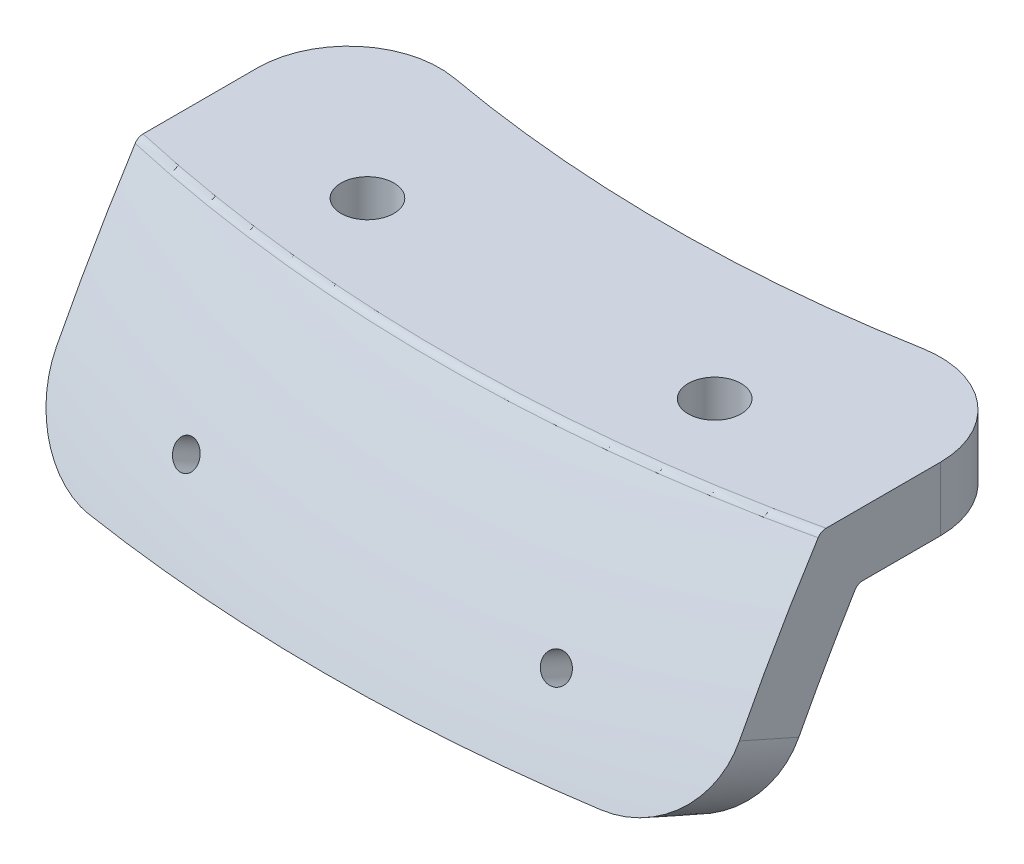
SolidWorks part; units mm, degrees
material "Polyether Polyol"
ref_plane "Front Plane" through (0, 0, 0) normal (0, 0, 1) x (1, 0, 0)
ref_plane "Top Plane" through (0, 0, 0) normal (0, 1, 0) x (1, 0, 0)
ref_plane "Right Plane" through (0, 0, 0) normal (1, 0, 0) x (0, 0, -1)
sketch "Sketch1" plane through (0, 0, 0) normal (1, 0, 0) x (0, 0, -1)
  line L0 (-182.3577, 155.0626) -> (-175.976, 152.1862) construction
  line L1 (-169.6296, 178.8688) -> (-144.7872, 178.8688) construction
  line L9 (-144.7872, 178.8688) -> (-144.7872, 171.8688) construction
  line L10 (-144.7872, 171.8688) -> (-165.7041, 171.8688) construction
  line L11 (-182.3577, 155.0626) -> (-175.976, 152.1862)
  line L12 (-169.6296, 178.8688) -> (-144.7872, 178.8688)
  line L13 (-144.7872, 178.8688) -> (-144.7872, 171.8688)
  line L14 (-144.7872, 171.8688) -> (-165.7041, 171.8688)
  line L15 (0, 0) -> (0, 72.8698) construction
  arc A5 (-165.7041, 171.8688) -> (-175.976, 152.1862) centre (0, 72.8698) ccw construction
  arc A6 (-169.6296, 178.8688) -> (-182.3577, 155.0626) centre (0, 72.8698) ccw construction
  arc A7 (-165.7041, 171.8688) -> (-175.976, 152.1862) centre (0, 72.8698) ccw
  arc A8 (-169.6296, 178.8688) -> (-182.3577, 155.0626) centre (0, 72.8698) ccw
revolve "Revolve1" add sketch "Sketch1" angle 30 mid plane about L15
sketch "Sketch2" plane through (0, 0, 0) normal (-1, 0, 0) x (0, 0, 1)
  line L0 (0, 72.8698) -> (171.9865, 160.5013) construction
  line L3 (0, -200000) -> (0, 218797.9879) construction
  arc A0 (175.976, 152.1862) -> (165.7041, 171.8688) centre (0, 72.8698) ccw construction
  dimension "D1" = 63
ref_plane "Plane1" through (0, 57.8508, -29.4764) normal (0, -0.891, 0.454) x (0, 0.454, 0.891)
sketch "Sketch4" plane through (0, 57.8508, -29.4764) normal (0, -0.891, 0.454) x (0, 0.454, 0.891)
  line L0 (200.4524, 17.5373) -> (239.1484, 20.9228) construction
  line L1 (200.3217, 19.0316) -> (239.0177, 22.4171)
  line L2 (200.3217, 19.0316) -> (200.4524, 17.5373)
  line L3 (33.0822, 0) -> (226.1072, 0) construction
  line L4 (200.4524, 17.5373) -> (239.1484, 20.9228)
  line L5 (239.0177, 22.4171) -> (239.1484, 20.9228)
  dimension "D1" = 3
  dimension "D2" = 5
revolve "Cut-Revolve1" cut sketch "Sketch4" angle 360 about L0
mirror "Mirror1" about plane through (0, 0, 0) normal (1, 0, 0) of "Cut-Revolve1"
sketch "Sketch5" plane through (0, 0, 0) normal (0, 1, 0) x (1, 0, 0)
  line L1 (37.4737, -139.8537) -> (-37.4737, -139.8537)
  line L2 (37.4737, -139.8537) -> (37.4737, -182.3577)
  line L3 (37.4737, -182.3577) -> (-37.4737, -182.3577)
  line L4 (-37.4737, -139.8537) -> (-37.4737, -182.3577)
  arc A0 (-47.1977, -176.1441) -> (47.1977, -176.1441) centre (0, 0) ccw construction
extrude "Cut-Extrude2" cut sketch "Sketch5" along normal through all flip side to cut
fillet "Fillet1" radius 10 4 edges at (-37.4737, 175.3688, 139.8537) (37.4737, 175.3688, 139.8537)
fillet "Fillet2" radius 1 2 edges at (0, 178.8688, 169.6296) (0, 171.8688, 165.7041)
sketch "Sketch6" plane through (0, 178.8688, 0) normal (0, 1, 0) x (1, 0, 0)
  circle A0 centre (19.05, -158.6742) radius 2.9 construction
  circle A1 centre (-19.05, -158.6742) radius 2.9 construction
  circle A2 centre (19.05, -158.6742) radius 2.9
  circle A3 centre (-19.05, -158.6742) radius 2.9
extrude "Cut-Extrude3" cut sketch "Sketch6" against normal through all
